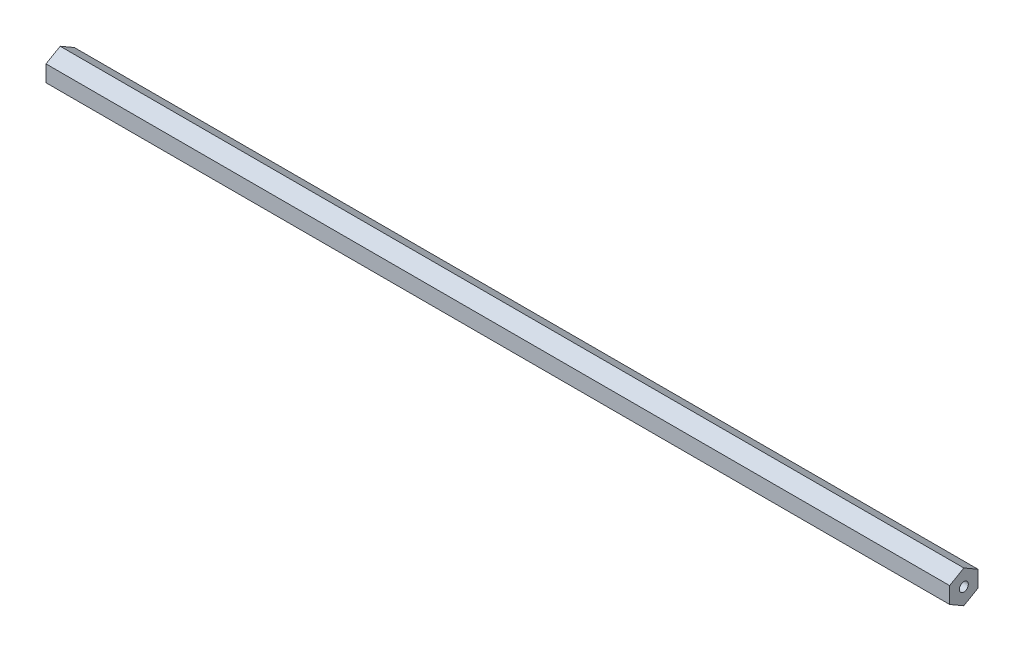
SolidWorks part; units mm, degrees
material "7075-T6 (SN)"
ref_plane "Front Plane" through (0, 0, 0) normal (0, 0, 1) x (1, 0, 0)
ref_plane "Top Plane" through (0, 0, 0) normal (0, 1, 0) x (1, 0, 0)
ref_plane "Right Plane" through (0, 0, 0) normal (1, 0, 0) x (0, 0, -1)
sketch "Sketch1" plane through (0, 0, 0) normal (1, 0, 0) x (0, 0, -1)
  line L1 (0, 7.3323) -> (-6.35, 3.6662)
  line L2 (-6.35, 3.6662) -> (-6.35, -3.6662)
  line L3 (-6.35, -3.6662) -> (0, -7.3323)
  line L4 (0, -7.3323) -> (6.35, -3.6662)
  line L5 (6.35, -3.6662) -> (6.35, 3.6662)
  line L6 (6.35, 3.6662) -> (0, 7.3323)
  circle A2 centre (0, 0) radius 6.35 construction
  dimension "D2" = 12.7
extrude "Boss-Extrude1" add sketch "Sketch1" along normal mid plane 404.8125 contours L5 L6 L1 L2 L3 L4 region at (0, 0, 0)
sketch "Sketch3" plane through (-200.025, 0, 0) normal (-1, 0, 0) x (0, 0, 1)
  circle A0 centre (0, 0) radius 6.35
  dimension "D1" = 12.7
hole_wizard "#10-32 Tapped Hole1" positions "3DSketch1" profile "Sketch4" tap size "#10-32" standard "ANSI Inch"
sketch3d "3DSketch1"
  point P10 (202.4062, 0, 0)
  point P13 (-202.4062, 0, 0)
sketch "Sketch4" plane through (202.4062, 0, 0) normal (0, 1, 0) x (0, 0, -1)
  line L0 (0, 0) -> (0, 17.5608)
  line L1 (0, 17.5608) -> (2.0193, 16.3474)
  line L2 (2.0193, 16.3474) -> (2.0193, 0)
  line L5 (2.0193, 0) -> (0, 0)
  line L10 (0, 17.5608) -> (-2.0193, 16.3474) construction
  line L11 (0, -6.35) -> (0, 107.95) construction
  dimension "Tap Drill Dia." = 4.0386
  dimension "Tap Drill Depth" = 16.3474
  dimension "Drill Angle" = 118
cosmetic thread "Hole Thread1" parameters "D1"=13.97, "D2"=4.826
cosmetic thread "Hole Thread2" parameters "D1"=13.97, "D2"=4.826
